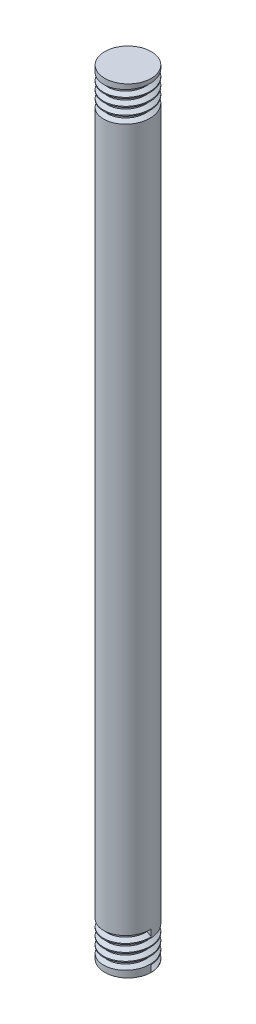
SolidWorks part; units mm, degrees
ref_plane "Front Plane" through (0, 0, 0) normal (0, 0, 1) x (1, 0, 0)
ref_plane "Top Plane" through (0, 0, 0) normal (0, 1, 0) x (1, 0, 0)
ref_plane "Right Plane" through (0, 0, 0) normal (1, 0, 0) x (0, 0, -1)
sketch "Sketch1" plane through (0, 0, 0) normal (0, 1, 0) x (1, 0, 0)
  circle A0 centre (0, 0) radius 3
  dimension "D1" = 6
extrude "Body" add sketch "Sketch1" along normal mid plane 100
thread "Thread1" pitch 1 method cut profile "Thread Profile1" start angle 0, offset 0, length 4, pitch 1, diameter 6
ref_plane "Plane1" through (-3, 50, 0) normal (0, 0, 1) x (-1, 0, 0)
sketch "Thread Profile1" plane through (-3, 50, 0) normal (0, 0, 1) x (-1, 0, 0)
  line L0 (0, 0) -> (0, 1) construction
  line L11 (0, 0) -> (0, 0.875)
  line L12 (0, 0.875) -> (-0.5413, 0.5625)
  line L13 (-0.5413, 0.5625) -> (-0.5413, 0.3125)
  line L15 (-0.5413, 0.3125) -> (0, 0)
  line L17 (-0.5413, 0.4375) -> (0, 0.4375) construction
  point P2 (0, 0)
  dimension "Pitch" = 1
  dimension "Profile_Angle" = 60
  dimension "Profile_Land" = 0.25
  dimension "Profile_Height" = 0.5413
thread "Thread2" pitch 1 method cut profile "Thread Profile2" start angle 0, offset 0, length 4, pitch 1, diameter 6
ref_plane "Plane2" through (3, -50, 0) normal (0, 0, 1) x (1, 0, 0)
sketch "Thread Profile2" plane through (3, -50, 0) normal (0, 0, 1) x (1, 0, 0)
  line L0 (0, 0) -> (0, 1) construction
  line L11 (0, 0) -> (0, 0.875)
  line L12 (0, 0.875) -> (-0.5413, 0.5625)
  line L13 (-0.5413, 0.5625) -> (-0.5413, 0.3125)
  line L15 (-0.5413, 0.3125) -> (0, 0)
  line L17 (-0.5413, 0.4375) -> (0, 0.4375) construction
  point P2 (0, 0)
  dimension "Pitch" = 1
  dimension "Profile_Angle" = 60
  dimension "Profile_Land" = 0.25
  dimension "Profile_Height" = 0.5413
